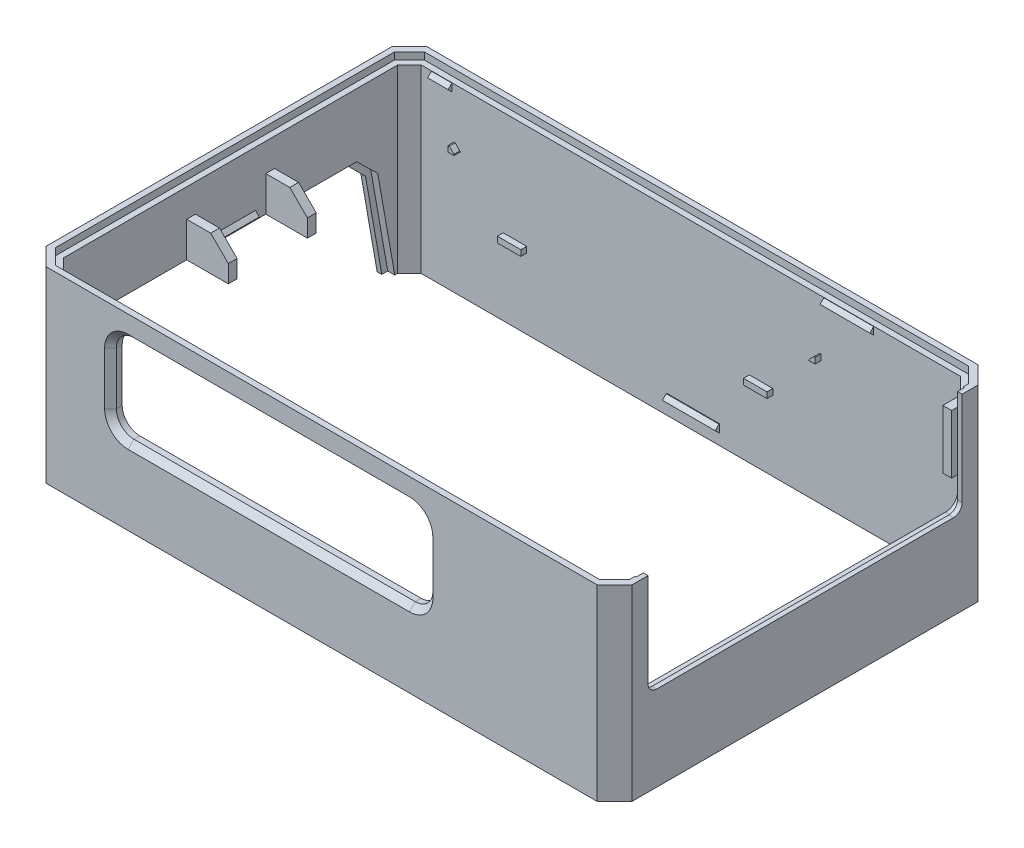
SolidWorks part; units mm, degrees
ref_plane "前视基准面" through (0, 0, 0) normal (0, 0, 1) x (1, 0, 0)
ref_plane "上视基准面" through (0, 0, 0) normal (0, 1, 0) x (1, 0, 0)
ref_plane "右视基准面" through (0, 0, 0) normal (1, 0, 0) x (0, 0, -1)
sketch "草图1" plane through (0, 0, 0) normal (0, 1, 0) x (1, 0, 0)
  line L1 (-50, 32.5) -> (50, 32.5)
  line L2 (-50, 32.5) -> (-50, -32.5)
  line L3 (-50, -32.5) -> (50, -32.5)
  line L4 (50, 32.5) -> (50, -32.5)
  line L5 (-50, 32.5) -> (50, -32.5) construction
  line L6 (-50, -32.5) -> (50, 32.5) construction
  point P0 (0, 0)
  dimension "D1" = 65
  dimension "D2" = 100
extrude "凸台-拉伸1" add sketch "草图1" along normal blind 32
sketch "草图2" plane through (0, 32, 0) normal (0, 1, 0) x (1, 0, 0)
  line L8 (48, -30.5) -> (48, 30.5)
  line L9 (48, 30.5) -> (-48, 30.5)
  line L10 (-48, 30.5) -> (-48, -30.5)
  line L11 (-48, -30.5) -> (48, -30.5)
  line L12 (48, -30.5) -> (48, 30.5)
  line L13 (48, 30.5) -> (-48, 30.5)
  line L14 (-48, 30.5) -> (-48, -30.5)
  line L15 (-48, -30.5) -> (48, -30.5)
  dimension "D1" = 2
extrude "切除-拉伸1" cut sketch "草图2" against normal through all
sketch "草图4" plane through (-50, 0, 0) normal (-1, 0, 0) x (0, 0, 1)
  line L0 (-32.5, 0) -> (32.5, 0) construction
  line L3 (-28, 0) -> (28, 0)
  line L7 (-25.0863, 16.5) -> (-21.5, 20)
  line L8 (21.5, 20) -> (25.09, 16.5)
  line L9 (32.5, 32) -> (32.5, 0) construction
  line L12 (-25.0863, 16.5) -> (-28, 0)
  line L13 (-21.5, 20) -> (21.5, 20)
  line L14 (25.09, 16.5) -> (28, 0)
  line L15 (-32.5, 0) -> (32.5, 0) construction
  line L16 (-32.5, 32) -> (-32.5, 0) construction
  dimension "D1" = 16.5
  dimension "D2" = 20
  dimension "D3" = 4.5
  dimension "D4" = 4.5
  dimension "D5" = 11
  dimension "D6" = 11
  dimension "D7" = 7.4137
  dimension "D8" = 7.41
extrude "切除-拉伸2" cut sketch "草图4" against normal blind 2
sketch "草图7" plane through (0, 0, 32.5) normal (0, 0, 1) x (1, 0, 0)
  line L0 (-50, 32) -> (-50, 0) construction
  line L5 (-50, 32) -> (50, 32) construction
  line L16 (-36, 28) -> (-36, 13)
  line L17 (18, 28) -> (-36, 28)
  line L18 (18, 13) -> (18, 28)
  line L19 (-36, 13) -> (18, 13)
  dimension "D1" = 54
  dimension "D2" = 15
  dimension "D3" = 14
  dimension "D4" = 4
extrude "切除-拉伸3" cut sketch "草图7" against normal blind 2.5
fillet "圆角7" radius 3 4 edges at (-36, 28, 31.5) (18, 28, 31.5) (18, 13, 31.5) (-36, 13, 31.5)
chamfer "倒角1" distance 1 angle 45 8 edges at (-9, 28, 32.5) (-35.1213, 27.1213, 32.5) (17.1213, 27.1213, 32.5) (-36, 20.5, 32.5) (18, 20.5, 32.5) (-35.1213, 13.8787, 32.5) (17.1213, 13.8787, 32.5) (-9, 13, 32.5)
ref_plane "基准面4" through (0, 19.25, 0) normal (0, -1, 0) x (-1, 0, 0)
sketch "草图17" plane through (-48, 0, 0) normal (1, 0, 0) x (0, 0, -1)
  line L1 (-6, 20) -> (-7.5, 20)
  line L2 (-6, 20) -> (-6, 26)
  line L3 (-6, 26) -> (-7.5, 26)
  line L4 (-7.5, 20) -> (-7.5, 26)
  line L5 (32.5, 32) -> (32.5, 0) construction
  line L6 (6, 20) -> (7.5, 20)
  line L7 (6, 20) -> (6, 26)
  line L8 (6, 26) -> (7.5, 26)
  line L9 (7.5, 20) -> (7.5, 26)
  line L10 (-21.5, 20) -> (21.5, 20) construction
  line L12 (-32.5, 32) -> (-32.5, 0) construction
  dimension "D1" = 1.5
  dimension "D2" = 1.5
  dimension "D3" = 25
  dimension "D4" = 25
  dimension "D5" = 6
extrude "凸台-拉伸6" add sketch "草图17" along normal blind 7.1
chamfer "倒角6" distance 3 angle 45 2 edges at (-40.9, 26, -6.75) (-40.9, 26, 6.75)
sketch "草图24" plane through (48, 0, 0) normal (-1, 0, 0) x (0, 0, 1)
  line L1 (-4.5, 3.3) -> (4.5, 3.3)
  line L2 (-4.5, 3.3) -> (-4.5, 1.8)
  line L3 (-4.5, 1.8) -> (4.5, 1.8)
  line L4 (4.5, 3.3) -> (4.5, 1.8)
  line L5 (-4.5, 3.3) -> (4.5, 1.8) construction
  line L6 (-4.5, 1.8) -> (4.5, 3.3) construction
  line L7 (30.5, 0) -> (-30.5, 0) construction
  line L8 (32.5, 0) -> (-32.5, 0) construction
  point P0 (0, 2.55)
  point P10 (0, 0)
  dimension "D1" = 1.5
  dimension "D2" = 1.8
  dimension "D3" = 9
extrude "凸台-拉伸10" add sketch "草图24" along normal blind 1
sketch "草图25" plane through (0, 0, 30.5) normal (0, 0, -1) x (-1, 0, 0)
  line L0 (48, 0) -> (-48, 0) construction
  line L1 (-4.9102, 3.2365) -> (4.0898, 3.2365)
  line L2 (-4.9102, 3.2365) -> (-4.9102, 1.9365)
  line L3 (-4.9102, 1.9365) -> (4.0898, 1.9365)
  line L4 (4.0898, 3.2365) -> (4.0898, 1.9365)
  line L5 (-4.9102, 3.2365) -> (4.0898, 1.9365) construction
  line L6 (-4.9102, 1.9365) -> (4.0898, 3.2365) construction
  line L8 (50, 32) -> (50, 0) construction
  point P0 (-0.4102, 2.5865)
  dimension "D1" = 9
  dimension "D2" = 1.3
  dimension "D3" = 2.5865
  dimension "D4" = 50.4102
extrude "凸台-拉伸11" add sketch "草图25" along normal blind 1
sketch "草图26" plane through (0, 0, -30.5) normal (0, 0, 1) x (1, 0, 0)
  line L4 (-4.0898, 3.2365) -> (-4.0898, 1.9365)
  line L5 (4.9102, 3.2365) -> (-4.0898, 3.2365)
  line L6 (4.9102, 1.9365) -> (4.9102, 3.2365)
  line L7 (-4.0898, 1.9365) -> (4.9102, 1.9365)
  line L8 (-4.0898, 3.2365) -> (-4.0898, 1.9365)
  line L9 (4.9102, 3.2365) -> (-4.0898, 3.2365)
  line L10 (4.9102, 1.9365) -> (4.9102, 3.2365)
  line L11 (-4.0898, 1.9365) -> (4.9102, 1.9365)
  dimension "D1" = 0
extrude "凸台-拉伸12" add sketch "草图26" along normal blind 1
chamfer "倒角7" distance 2 angle 45 4 edges at (-48, 16, -30.5) (-48, 16, 30.5) (48, 16, -30.5) (48, 16, 30.5)
chamfer "倒角8" distance 3 angle 45 4 edges at (-50, 16, 32.5) (-50, 16, -32.5) (50, 16, -32.5) (50, 16, 32.5)
sketch "草图28" plane through (-50, 0, 0) normal (-1, 0, 0) x (0, 0, 1)
  line L27 (-29.3, 22.3393) -> (-29.3, 0)
  line L28 (-29.3, 0) -> (-26.9872, 0)
  line L29 (-26.9872, 0) -> (-24.2154, 15.8784)
  line L30 (-24.2154, 15.8784) -> (-21.1176, 18.9896)
  line L31 (-21.1176, 18.9896) -> (21.1176, 18.9896)
  line L32 (21.1176, 18.9896) -> (24.2152, 15.8784)
  line L33 (24.2152, 15.8784) -> (27.008, 0)
  line L34 (27.008, 0) -> (29.3, 0)
  line L35 (29.3, 0) -> (29.3, 22.3393)
  line L36 (29.3, 22.3393) -> (-29.3, 22.3393)
  line L37 (28.5, 0) -> (-28.5, 0) construction
  line L38 (-29.5, 0) -> (-28, 0) construction
  line L39 (28, 0) -> (29.5, 0) construction
extrude "凸台-拉伸13" add sketch "草图28" against normal blind 0.8
sketch "草图35" plane through (48, 0, 0) normal (-1, 0, 0) x (0, 0, 1)
  line L0 (-28, 32) -> (28, 32)
  line L1 (-28, 32) -> (-28, 14)
  line L2 (-28, 14) -> (28, 14)
  line L3 (28, 32) -> (28, 14)
  line L4 (32.5, 0) -> (32.5, 32) construction
  line L5 (-32.5, 32) -> (-32.5, 0) construction
  line L6 (28.5, 32) -> (-28.5, 32) construction
  dimension "D1" = 18
  dimension "D3" = 4.5
  dimension "D4" = 4.5
extrude "切除-拉伸6" cut sketch "草图35" against normal blind 1.2
fillet "圆角17" radius 2 2 edges at (48.6, 14, -28) (48.6, 14, 28)
sketch "草图39" plane through (49.2, 0, 0) normal (-1, 0, 0) x (0, 0, 1)
  line L0 (32.5, 0) -> (32.5, 32) construction
  line L1 (-32.5, 32) -> (-32.5, 0) construction
  line L2 (28, 32) -> (-28, 32) construction
  line L3 (29.5, 32) -> (-29.5, 32) construction
  line L4 (29.5, 0) -> (-29.5, 0) construction
  line L12 (-26.8, 32) -> (-26.8, 16)
  line L13 (-25.3, 14.5) -> (25.3, 14.5)
  line L14 (26.8, 16) -> (26.8, 32)
  line L15 (26.8, 32) -> (-26.8, 32)
  arc A6 (-26.8, 16) -> (-25.3, 14.5) centre (-25.3, 16) ccw
  arc A7 (25.3, 14.5) -> (26.8, 16) centre (25.3, 16) ccw
  dimension "D1" = 7.2
  dimension "D2" = 7.2
  dimension "D3" = 16
  dimension "D4" = 14.5
extrude "切除-拉伸7" cut sketch "草图39" against normal blind 1.2
ref_plane "基准面5" through (-50, 32, 29.5) normal (0.7071, 0, 0.7071) x (0.7071, 0, -0.7071)
sketch "草图44" plane through (0, 0, -28) normal (0, 0, 1) x (1, 0, 0)
  line L0 (48, 32) -> (48, 16) construction
  line L1 (48, 28.5) -> (46.5, 28.5)
  line L2 (48, 28.5) -> (48, 18.5)
  line L3 (48, 18.5) -> (46.5, 18.5)
  line L4 (46.5, 28.5) -> (46.5, 18.5)
  line L5 (50, 14.5) -> (49.2, 14.5) construction
  dimension "D1" = 1.5
  dimension "D2" = 10
  dimension "D3" = 4
extrude "凸台-拉伸15" add sketch "草图44" along normal blind 1 and the other way up to surface (2.5 mm away) other way up to face at (0, 16, -30.5)
sketch "草图45" plane through (0, 0, 28) normal (0, 0, -1) x (-1, 0, 0)
  line L4 (-48, 28.5) -> (-48, 18.5)
  line L5 (-46.5, 28.5) -> (-48, 28.5)
  line L6 (-46.5, 18.5) -> (-46.5, 28.5)
  line L7 (-48, 18.5) -> (-46.5, 18.5)
  line L8 (-48, 28.5) -> (-48, 18.5)
  line L9 (-46.5, 28.5) -> (-48, 28.5)
  line L10 (-46.5, 18.5) -> (-46.5, 28.5)
  line L11 (-48, 18.5) -> (-46.5, 18.5)
  dimension "D1" = 0
extrude "凸台-拉伸16" add sketch "草图45" along normal blind 1 and the other way up to surface (2.5 mm away) other way up to face at (0, 16, 30.5)
ref_plane "基准面6" through (48, 0, -28.5) normal (0, 0, -1) x (-1, 0, 0)
sketch "草图48" plane through (0, 32, 0) normal (0, 1, 0) x (1, 0, 0)
  line L0 (48, 28.5) -> (46, 30.5)
  line L1 (46, 30.5) -> (-46, 30.5)
  line L2 (48, 28.5) -> (48, -28.5)
  line L3 (46, -30.5) -> (-46, -30.5)
  line L4 (-48, 28.5) -> (-48, -28.5)
  line L5 (48, -28.5) -> (46, -30.5)
  line L6 (-46, -30.5) -> (-48, -28.5)
  line L7 (-46, 30.5) -> (-48, 28.5)
  line L8 (49, 28.9142) -> (49, -28.9142)
  line L9 (49, -28.9142) -> (46.4142, -31.5)
  line L10 (46.4142, -31.5) -> (-46.4142, -31.5)
  line L11 (-46.4142, -31.5) -> (-49, -28.9142)
  line L12 (-49, 28.9142) -> (-49, -28.9142)
  line L13 (-46.4142, 31.5) -> (-49, 28.9142)
  line L14 (46.4142, 31.5) -> (-46.4142, 31.5)
  line L15 (49, 28.9142) -> (46.4142, 31.5)
  point P0 (48, 30.5)
  point P1 (-48, -30.5)
  point P2 (48, -30.5)
  point P3 (-48, 30.5)
  dimension "D2" = 1
extrude "切除-拉伸8" cut sketch "草图48" against normal blind 1.2
sketch "草图49" plane through (0, 0, -30.5) normal (0, 0, 1) x (1, 0, 0)
  line L0 (50, 32) -> (50, 16) construction
  line L1 (22.6985, 30.75) -> (31.1985, 30.75)
  line L2 (22.6985, 30.75) -> (22.6985, 29.45)
  line L3 (22.6985, 29.45) -> (31.1985, 29.45)
  line L4 (31.1985, 30.75) -> (31.1985, 29.45)
  line L5 (22.6985, 30.75) -> (31.1985, 29.45) construction
  line L6 (22.6985, 29.45) -> (31.1985, 30.75) construction
  line L7 (-47, 32) -> (47, 32) construction
  line L8 (46.4142, 32) -> (-46.4142, 32) construction
  line L9 (-44.25, 30.75) -> (-40.75, 30.75)
  line L10 (-44.25, 30.75) -> (-44.25, 29.45)
  line L11 (-44.25, 29.45) -> (-40.75, 29.45)
  line L12 (-40.75, 30.75) -> (-40.75, 29.45)
  line L13 (-44.25, 30.75) -> (-40.75, 29.45) construction
  line L14 (-44.25, 29.45) -> (-40.75, 30.75) construction
  line L15 (-50, 0) -> (-50, 32) construction
  point P0 (26.9485, 30.1)
  point P7 (-42.5, 30.1)
  dimension "D1" = 1.3
  dimension "D2" = 8.5
  dimension "D3" = 18.8015
  dimension "D4" = 1.9
  dimension "D5" = 1.3
  dimension "D6" = 1.9
  dimension "D7" = 5.75
  dimension "D8" = 3.5
extrude "凸台-拉伸17" add sketch "草图49" along normal blind 0.8
sketch "草图50" plane through (0, 0, 30.5) normal (0, 0, -1) x (-1, 0, 0)
  line L0 (40.75, 29.45) -> (40.75, 30.75) construction
  line L1 (40.75, 30.75) -> (44.25, 30.75) construction
  line L2 (44.25, 30.75) -> (44.25, 29.45) construction
  line L3 (44.25, 29.45) -> (40.75, 29.45) construction
  line L4 (-31.1985, 29.45) -> (-31.1985, 30.75) construction
  line L5 (-31.1985, 30.75) -> (-22.6985, 30.75) construction
  line L6 (-22.6985, 30.75) -> (-22.6985, 29.45) construction
  line L7 (-22.6985, 29.45) -> (-31.1985, 29.45) construction
  line L12 (40.75, 29.45) -> (40.75, 30.75)
  line L13 (40.75, 30.75) -> (44.25, 30.75)
  line L14 (44.25, 30.75) -> (44.25, 29.45)
  line L15 (44.25, 29.45) -> (40.75, 29.45)
  line L16 (-31.1985, 29.45) -> (-31.1985, 30.75)
  line L17 (-31.1985, 30.75) -> (-22.6985, 30.75)
  line L18 (-22.6985, 30.75) -> (-22.6985, 29.45)
  line L19 (-22.6985, 29.45) -> (-31.1985, 29.45)
extrude "凸台-拉伸18" add sketch "草图50" along normal blind 0.8
sketch "草图55" plane through (0, 0, -30.5) normal (0, 0, 1) x (1, 0, 0)
  line L0 (-50, 0) -> (-50, 32) construction
  line L1 (-23, 20) -> (5.5, 20)
  line L2 (-23, 20) -> (-23, 18.6)
  line L3 (-23, 18.6) -> (5.5, 18.6)
  line L4 (5.5, 20) -> (5.5, 18.6)
  line L5 (-47, 32) -> (47, 32) construction
  dimension "D1" = 1.4
  dimension "D2" = 27
  dimension "D3" = 12
  dimension "D4" = 28.5
sketch "草图56" plane through (0, 0, -30.5) normal (0, 0, 1) x (1, 0, 0)
  line L0 (-50, 0) -> (-50, 32) construction
  line L1 (-23, 24) -> (-21.5, 24)
  line L2 (-23, 24) -> (-23, 16)
  line L3 (-23, 16) -> (-21.5, 16)
  line L4 (-21.5, 24) -> (-21.5, 16)
  line L5 (4, 24) -> (5.5, 24)
  line L6 (4, 24) -> (4, 16)
  line L7 (4, 16) -> (5.5, 16)
  line L8 (5.5, 24) -> (5.5, 16)
  line L9 (-47, 32) -> (47, 32) construction
  dimension "D1" = 1.5
  dimension "D2" = 8
  dimension "D3" = 27
  dimension "D4" = 54
  dimension "D5" = 8
chamfer "倒角11" distance 0.8 angle 45 8 edges at (-42.5, 30.75, 29.7) (-42.5, 29.45, 29.7) (26.9485, 29.45, -29.7) (26.9485, 30.75, -29.7) (26.9485, 30.75, 29.7) (26.9485, 29.45, 29.7) (-42.5, 29.45, -29.7) (-42.5, 30.75, -29.7)
chamfer "倒角12" distance 0.9 angle 45 4 edges at (0.4102, 1.9365, 29.5) (0.4102, 3.2365, 29.5) (0.4102, 1.9365, -29.5) (0.4102, 3.2365, -29.5)
chamfer "倒角13" distance 0.9 angle 45 2 edges at (47, 1.8, 0) (47, 3.3, 0)
sketch "草图57" plane through (0, 0, 30.5) normal (0, 0, -1) x (-1, 0, 0)
  line L1 (-21.2, 21.2) -> (-22.2, 21.2)
  line L2 (-21.2, 21.2) -> (-21.2, 22.2)
  line L3 (-21.2, 22.2) -> (-22.2, 22.2)
  line L4 (-22.2, 21.2) -> (-22.2, 22.2)
  line L5 (39.4, 21.2) -> (40.4, 21.2)
  line L6 (39.4, 21.2) -> (39.4, 22.2)
  line L7 (39.4, 22.2) -> (40.4, 22.2)
  line L8 (40.4, 21.2) -> (40.4, 22.2)
  line L9 (47, 32) -> (-47, 32) construction
  line L10 (-50, 32) -> (-50, 0) construction
  line L11 (50, 0) -> (50, 32) construction
  line L12 (46, 0) -> (-46, 0) construction
  line L17 (-14, 9) -> (-10, 9)
  line L18 (-14, 9) -> (-14, 8)
  line L19 (-14, 8) -> (-10, 8)
  line L20 (-10, 9) -> (-10, 8)
  line L21 (28, 9) -> (32, 9)
  line L22 (28, 9) -> (28, 8)
  line L23 (28, 8) -> (32, 8)
  line L24 (32, 9) -> (32, 8)
  point P24 (0, 0)
  dimension "D1" = 1
  dimension "D2" = 10.8
  dimension "D3" = 28.8
  dimension "D4" = 10.6
  dimension "D5" = 4
  dimension "D6" = 4
  dimension "D7" = 1
  dimension "D8" = 1
  dimension "D9" = 9
  dimension "D10" = 18
  dimension "D11" = 60
extrude "凸台-拉伸24" add sketch "草图57" along normal blind 1
chamfer "倒角14" distance 0.8 angle 45 2 edges at (21.2, 22.2, 30) (-39.4, 22.2, 30)
sketch "草图58" plane through (0, 0, -30.5) normal (0, 0, 1) x (1, 0, 0)
  line L0 (21.2, 21.2) -> (21.2, 21.4) construction
  line L1 (21.2, 21.4) -> (22, 22.2) construction
  line L2 (22, 22.2) -> (22.2, 22.2) construction
  line L3 (22.2, 22.2) -> (22.2, 21.2) construction
  line L4 (22.2, 21.2) -> (21.2, 21.2) construction
  line L5 (-40.4, 22.2) -> (-40.2, 22.2) construction
  line L6 (-40.2, 22.2) -> (-39.4, 21.4) construction
  line L7 (-39.4, 21.4) -> (-39.4, 21.2) construction
  line L8 (-39.4, 21.2) -> (-40.4, 21.2) construction
  line L9 (-40.4, 21.2) -> (-40.4, 22.2) construction
  line L10 (21.2, 21.2) -> (21.2, 21.4)
  line L11 (21.2, 21.4) -> (22, 22.2)
  line L12 (22, 22.2) -> (22.2, 22.2)
  line L13 (22.2, 22.2) -> (22.2, 21.2)
  line L14 (22.2, 21.2) -> (21.2, 21.2)
  line L15 (-40.4, 22.2) -> (-40.2, 22.2)
  line L16 (-40.2, 22.2) -> (-39.4, 21.4)
  line L17 (-39.4, 21.4) -> (-39.4, 21.2)
  line L18 (-39.4, 21.2) -> (-40.4, 21.2)
  line L19 (-40.4, 21.2) -> (-40.4, 22.2)
  line L28 (14, 13) -> (14, 12)
  line L29 (14, 12) -> (10, 12)
  line L30 (10, 12) -> (10, 13)
  line L31 (10, 13) -> (14, 13)
  line L32 (-28, 13) -> (-28, 12)
  line L33 (-28, 12) -> (-32, 12)
  line L34 (-32, 12) -> (-32, 13)
  line L35 (-32, 13) -> (-28, 13)
  line L36 (-50, 32) -> (-50, 0) construction
  line L37 (46, 0) -> (-46, 0) construction
  point P6 (0, 0)
  point P9 (0, 0)
  point P14 (0, 0)
  point P16 (0, 0)
  point P20 (0, 0)
  point P22 (0, 0)
  dimension "D1" = 18
  dimension "D2" = 60
  dimension "D3" = 1
  dimension "D4" = 4
  dimension "D5" = 4
  dimension "D6" = 12
extrude "凸台-拉伸25" add sketch "草图58" along normal blind 1
sketch "草图59" plane through (-48, 0, 0) normal (1, 0, 0) x (0, 0, -1)
  line L0 (29.5, 32) -> (-29.5, 32) construction
  line L1 (-4.25, 21.4396) -> (4.25, 21.4396)
  line L2 (-4.25, 21.4396) -> (-4.25, 20.1396)
  line L3 (-4.25, 20.1396) -> (4.25, 20.1396)
  line L4 (4.25, 21.4396) -> (4.25, 20.1396)
  line L5 (-4.25, 21.4396) -> (4.25, 20.1396) construction
  line L6 (-4.25, 20.1396) -> (4.25, 21.4396) construction
  line L7 (21.1176, 18.9896) -> (-21.1176, 18.9896) construction
  point P0 (0, 20.7896)
  point P7 (0, 32)
  dimension "D1" = 8.5
  dimension "D2" = 1.3
  dimension "D3" = 1.8
extrude "凸台-拉伸26" add sketch "草图59" along normal blind 0.8
chamfer "倒角15" distance 0.8 angle 45 2 edges at (-47.2, 20.1396, 0) (-47.2, 21.4396, 0)
